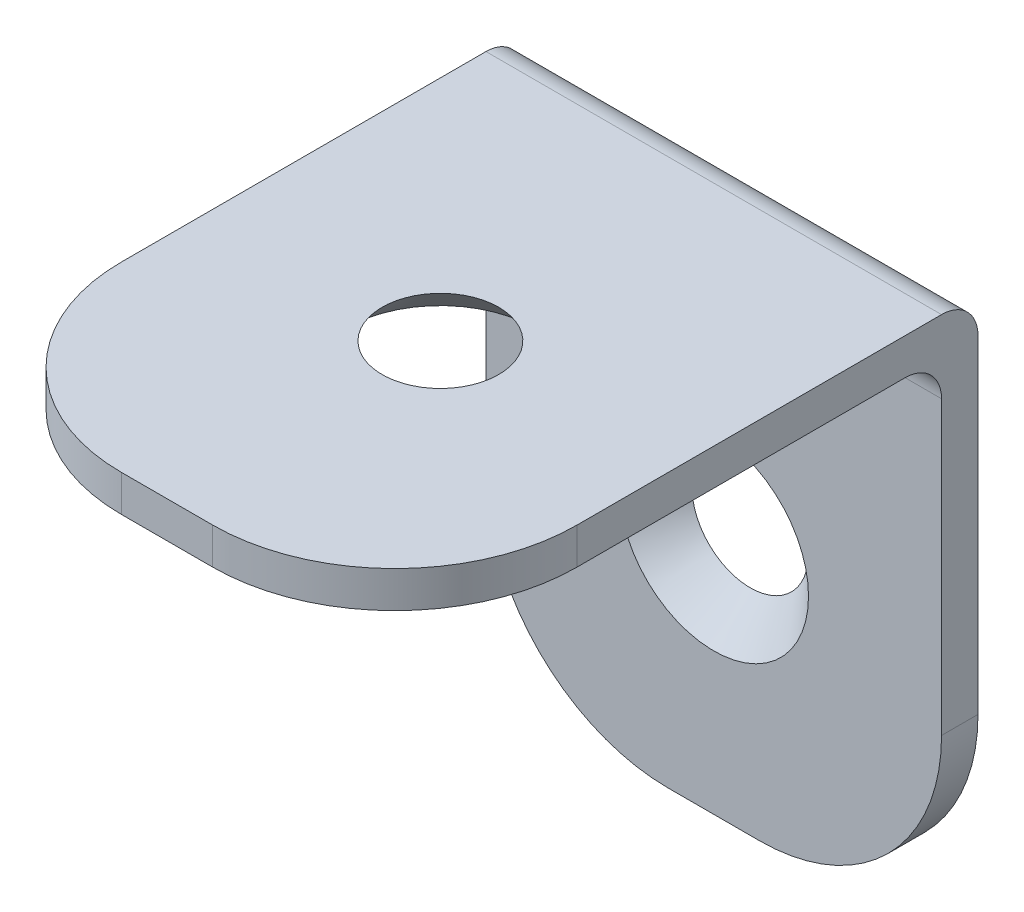
SolidWorks part; units mm, degrees
ref_plane "Спереди" through (0, 0, 0) normal (0, 0, 1) x (1, 0, 0)
ref_plane "Сверху" through (0, 0, 0) normal (0, 1, 0) x (1, 0, 0)
ref_plane "Справа" through (0, 0, 0) normal (1, 0, 0) x (0, 0, -1)
sketch "Эскиз1" plane through (0, 0, 0) normal (0, 1, 0) x (1, 0, 0)
  line L1 (-2.5, -15) -> (2.5, -15)
  line L2 (-12.5, -5) -> (-12.5, 15)
  line L3 (-12.5, 15) -> (12.5, 15)
  line L4 (12.5, -5) -> (12.5, 15)
  line L5 (-12.5, -15) -> (12.5, 15) construction
  line L6 (-12.5, 15) -> (12.5, -15) construction
  arc A0 (2.5, -15) -> (12.5, -5) centre (2.5, -5) ccw
  arc A1 (-2.5, -15) -> (-12.5, -5) centre (-2.5, -5) cw
  point P0 (0, 0)
  dimension "D3" = 10
  dimension "D1" = 25
  dimension "D2" = 30
extrude "Бобышка-Вытянуть1" add sketch "Эскиз1" along normal blind 2
sketch "Эскиз3" plane through (0, 0, -15) normal (0, 0, -1) x (-1, 0, 0)
  line L0 (-2.5, -28) -> (2.5, -28)
  line L1 (-12.5, -18) -> (-12.5, 2)
  line L2 (-12.5, 2) -> (12.5, 2)
  line L3 (12.5, -18) -> (12.5, 2)
  line L4 (-12.5, 0) -> (12.5, 0) construction
  arc A0 (2.5, -28) -> (12.5, -18) centre (2.5, -18) ccw
  arc A1 (-2.5, -28) -> (-12.5, -18) centre (-2.5, -18) cw
  point P8 (0, 0)
  point P9 (0, 0)
  dimension "D1" = 28
  dimension "D2" = 25
extrude "Бобышка-Вытянуть2" add sketch "Эскиз3" along normal blind 2
fillet "Скругление1" radius 2 1 edges at (0, 0, -15)
fillet "Скругление2" radius 2 1 edges at (0, 2, -17)
hole_wizard "Зенковка для винта с полупотайной головкой M52" positions "Эскиз6" profile "Эскиз7" countersink size "M5" standard "ISO" end condition through all
sketch "Эскиз6" plane through (0, 0, -15) normal (0, 0, 1) x (1, 0, 0)
  point P0 (0, -15.0342)
sketch "Эскиз7" plane through (0, -15.0342, -15) normal (1, 0, 0) x (0, -1, 0)
  line L0 (0, 0) -> (0, 2)
  line L1 (0, 2) -> (2.75, 2)
  line L2 (2.75, 2) -> (2.75, 2.45)
  line L3 (2.75, 2.45) -> (5.2, 0)
  line L5 (5.2, 0) -> (0, 0)
  line L6 (-2.75, 2.45) -> (-5.2, 0) construction
  line L11 (0, -6.35) -> (0, 107.95) construction
  dimension "Диаметр сквозного отверстия" = 5.5
  dimension "Глубина сквозного отверстия" = 2
  dimension "Диаметр передней зенковки" = 10.4
  dimension "Угол передней зенковки" = 90
hole_wizard "Зенковка для винта с полупотайной головкой M53" positions "Эскиз8" profile "Эскиз9" countersink size "M5" standard "ISO" end condition through all
sketch "Эскиз8" plane through (0, 0, 0) normal (0, -1, 0) x (-1, 0, 0)
  point P0 (0, 0)
sketch "Эскиз9" plane through (0, 0, 0) normal (1, 0, 0) x (0, 0, -1)
  line L0 (0, 0) -> (0, 2)
  line L1 (0, 2) -> (2.75, 2)
  line L2 (2.75, 2) -> (2.75, 2.45)
  line L3 (2.75, 2.45) -> (5.2, 0)
  line L5 (5.2, 0) -> (0, 0)
  line L6 (-2.75, 2.45) -> (-5.2, 0) construction
  line L11 (0, -6.35) -> (0, 107.95) construction
  dimension "Диаметр сквозного отверстия" = 5.5
  dimension "Глубина сквозного отверстия" = 2
  dimension "Диаметр передней зенковки" = 10.4
  dimension "Угол передней зенковки" = 90
